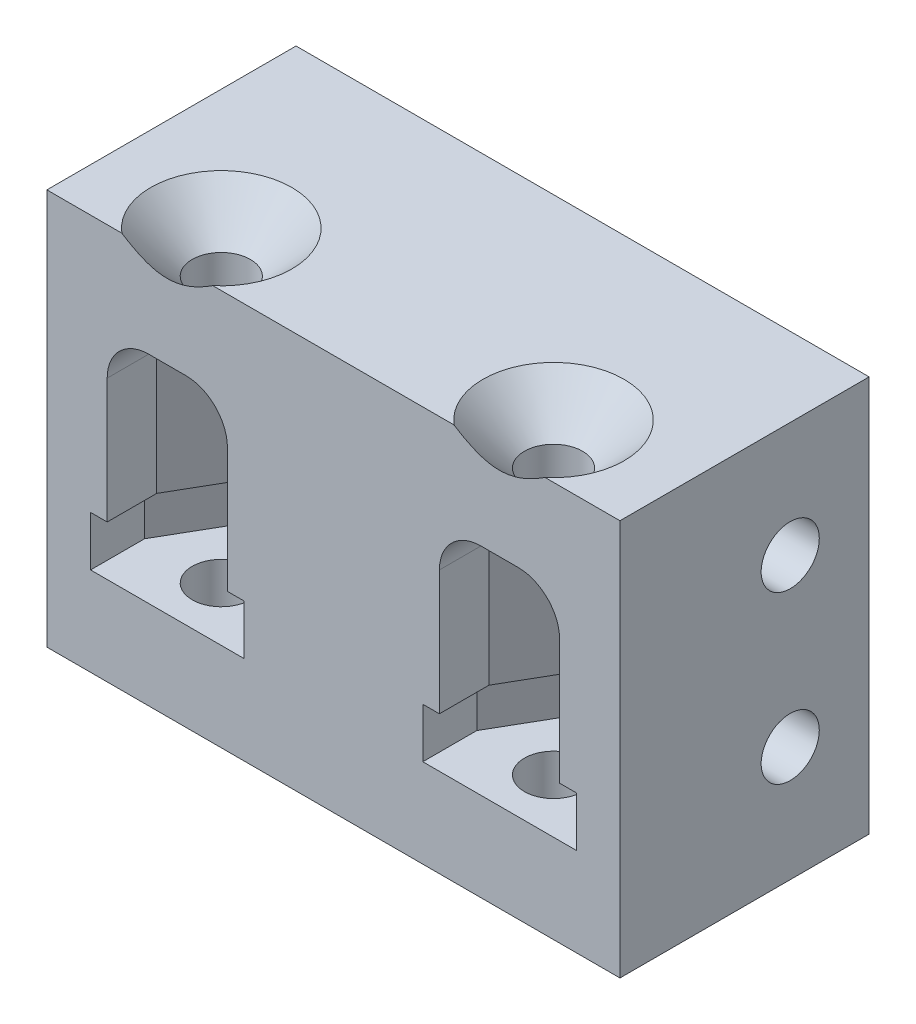
SolidWorks part; units mm, degrees
ref_plane "Front Plane" through (0, 0, 0) normal (0, 0, 1) x (1, 0, 0)
ref_plane "Top Plane" through (0, 0, 0) normal (0, 1, 0) x (1, 0, 0)
ref_plane "Right Plane" through (0, 0, 0) normal (1, 0, 0) x (0, 0, -1)
sketch "Sketch1" plane through (0, 0, 0) normal (1, 0, 0) x (0, 0, -1)
  line L0 (2.75, -5) -> (2.75, 5) construction
  line L1 (-7.5, -11.92) -> (7.5, -11.92)
  line L2 (-7.5, -11.92) -> (-7.5, 11.92)
  line L3 (-7.5, 11.92) -> (7.5, 11.92)
  line L4 (7.5, -11.92) -> (7.5, 11.92)
  line L5 (-7.5, -11.92) -> (7.5, 11.92) construction
  line L6 (-7.5, 11.92) -> (7.5, -11.92) construction
  circle A0 centre (2.75, 5) radius 1.75
  circle A1 centre (2.75, -5) radius 1.75
  point P0 (0, 0)
  point P11 (2.75, 0)
  point P12 (4.5, 5)
  dimension "D2" = 3.5
  dimension "D1" = 15
  dimension "D3" = 10
  dimension "D4" = 3
  dimension "D5" = 23.84
extrude "Boss-Extrude1" add sketch "Sketch1" along normal mid plane 34.5
sketch "Sketch2" plane through (0, 11.92, 0) normal (0, 1, 0) x (1, 0, 0)
  line L0 (-10, -4.25) -> (10, -4.25) construction
  line L1 (17.25, -7.5) -> (-17.25, -7.5) construction
  circle A0 centre (-10, -4.25) radius 1.75
  circle A1 centre (10, -4.25) radius 1.75
  point P5 (0, -4.25)
  point P6 (-10, -6)
  dimension "D1" = 3.5
  dimension "D2" = 20
  dimension "D3" = 1.5
extrude "Cut-Extrude1" cut sketch "Sketch2" against normal through all
chamfer "Chamfer1" distance 2.5 angle 45 2 edges at (10, 11.92, 6) (-10, 11.92, 6)
ref_plane "Plane1" through (0, -5.08, 0) normal (0, 1, 0) x (1, 0, 0)
sketch "Sketch3" plane through (0, -5.08, 0) normal (0, 1, 0) x (1, 0, 0)
  line L0 (-14.6188, -4.25) -> (-14.6188, -7.5)
  line L1 (-5.3812, -4.25) -> (-7.6906, -0.25)
  line L2 (-7.6906, -0.25) -> (-12.3094, -0.25)
  line L3 (-12.3094, -0.25) -> (-14.6188, -4.25)
  line L4 (-14.6188, -4.25) -> (-12.3094, -8.25) construction
  line L5 (-12.3094, -8.25) -> (-7.6906, -8.25) construction
  line L6 (-7.6906, -8.25) -> (-5.3812, -4.25) construction
  line L7 (14.6188, -4.25) -> (12.3094, -0.25)
  line L8 (12.3094, -0.25) -> (7.6906, -0.25)
  line L9 (7.6906, -0.25) -> (5.3812, -4.25)
  line L10 (5.3812, -4.25) -> (7.6906, -8.25) construction
  line L11 (7.6906, -8.25) -> (12.3094, -8.25) construction
  line L12 (12.3094, -8.25) -> (14.6188, -4.25) construction
  line L13 (-12.7386, -7.5) -> (-17.25, -7.5) construction
  line L14 (-14.6188, -7.5) -> (-5.3812, -7.5)
  line L15 (7.2614, -7.5) -> (-7.2614, -7.5) construction
  line L16 (-5.3812, -7.5) -> (-5.3812, -4.25)
  line L17 (5.3812, -4.25) -> (5.3812, -7.5)
  line L18 (5.3812, -7.5) -> (14.6188, -7.5)
  line L19 (17.25, -7.5) -> (12.7386, -7.5) construction
  line L20 (14.6188, -7.5) -> (14.6188, -4.25)
  circle A0 centre (-10, -4.25) radius 4 construction
  circle A1 centre (10, -4.25) radius 4 construction
  dimension "D1" = 8
extrude "Cut-Extrude2" cut sketch "Sketch3" against normal mid plane 3
sketch "Sketch4" plane through (0, -3.58, 0) normal (0, -1, 0) x (1, 0, 0)
  line L6 (-13.6188, 6.5) -> (-13.6188, 7.5)
  line L7 (17.25, 7.5) -> (-17.25, 7.5) construction
  line L8 (-13.6188, 7.5) -> (-6.3812, 7.5)
  line L9 (-6.3812, 7.5) -> (-6.3812, 6.5)
  line L12 (-6.3812, 4.5179) -> (-6.3812, 6.5)
  line L13 (-6.3812, 6.5) -> (-13.6188, 6.5)
  line L14 (-13.6188, 6.5) -> (-13.6188, 4.5179)
  line L15 (-13.6188, 4.5179) -> (-11.7321, 1.25)
  line L16 (-11.7321, 1.25) -> (-8.2679, 1.25)
  line L17 (-8.2679, 1.25) -> (-6.3812, 4.5179)
  line L18 (-6.3812, 4.5179) -> (-6.3812, 6.5)
  line L19 (-6.3812, 6.5) -> (-13.6188, 6.5) construction
  line L20 (-13.6188, 6.5) -> (-13.6188, 4.5179)
  line L21 (-13.6188, 4.5179) -> (-11.7321, 1.25)
  line L22 (-11.7321, 1.25) -> (-8.2679, 1.25)
  line L23 (-8.2679, 1.25) -> (-6.3812, 4.5179)
  line L28 (6.3812, 6.5) -> (6.3812, 7.5)
  line L29 (6.3812, 7.5) -> (13.6188, 7.5)
  line L30 (13.6188, 7.5) -> (13.6188, 6.5)
  line L34 (13.6188, 4.5179) -> (13.6188, 6.5)
  line L35 (13.6188, 6.5) -> (6.3812, 6.5)
  line L36 (6.3812, 6.5) -> (6.3812, 4.5179)
  line L37 (6.3812, 4.5179) -> (8.2679, 1.25)
  line L38 (8.2679, 1.25) -> (11.7321, 1.25)
  line L39 (11.7321, 1.25) -> (13.6188, 4.5179)
  line L40 (13.6188, 4.5179) -> (13.6188, 6.5)
  line L41 (13.6188, 6.5) -> (6.3812, 6.5) construction
  line L42 (6.3812, 6.5) -> (6.3812, 4.5179)
  line L43 (6.3812, 4.5179) -> (8.2679, 1.25)
  line L44 (8.2679, 1.25) -> (11.7321, 1.25)
  line L45 (11.7321, 1.25) -> (13.6188, 4.5179)
  dimension "D1" = 1
  dimension "D2" = 1
extrude "Cut-Extrude3" cut sketch "Sketch4" against normal blind 10
fillet "Fillet2" radius 2.5 10 edges at (13.6188, 6.42, 6.009) (12.6754, 6.42, 2.884) (10, 6.42, 1.25) (7.3246, 6.42, 2.884) (6.3812, 6.42, 6.009) (-13.6188, 6.42, 6.009) (-12.6754, 6.42, 2.884) (-10, 6.42, 1.25) (-7.3246, 6.42, 2.884) (-6.3812, 6.42, 6.009)
